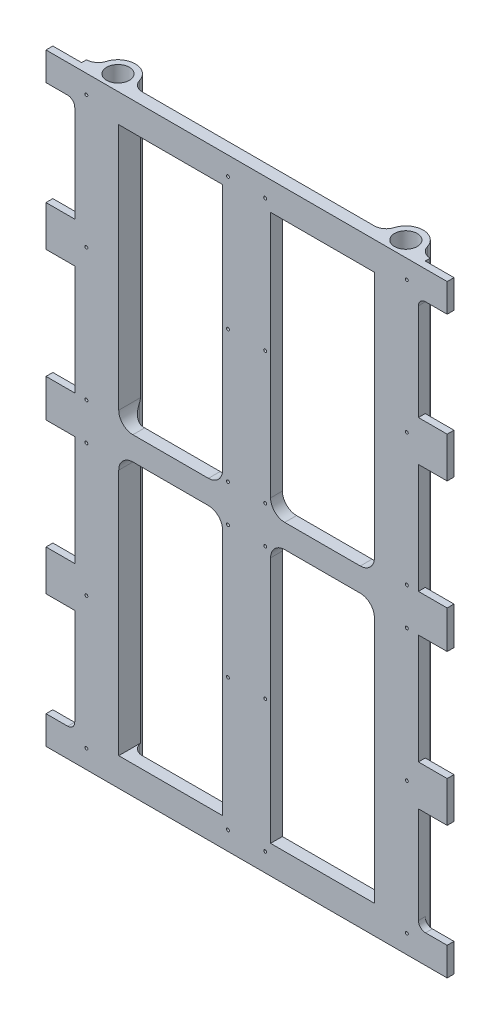
SolidWorks part; units mm, degrees
material "PLA"
ref_plane "Front Plane" through (0, 0, 0) normal (0, 0, 1) x (1, 0, 0)
ref_plane "Top Plane" through (0, 0, 0) normal (0, 1, 0) x (1, 0, 0)
ref_plane "Right Plane" through (0, 0, 0) normal (1, 0, 0) x (0, 0, -1)
other "Center of Mass"
sketch "Sketch1" plane through (0, 0, 0) normal (0, 1, 0) x (1, 0, 0)
  line L19 (85, -5) -> (85, 0)
  line L20 (85, -5) -> (-85, -5)
  line L24 (85, 0) -> (72.8176, 0)
  line L25 (-85, -5) -> (-85, 0)
  line L26 (85, -5) -> (-85, 0) construction
  line L27 (85, 0) -> (-85, -5) construction
  line L28 (0, 0) -> (0, -5) construction
  line L29 (-72.8176, 0) -> (-85, 0)
  line L30 (49.1824, 0) -> (-49.1824, 0)
  circle A29 centre (-61, 1.5) radius 4.825
  arc A30 (-68.1698, 0) -> (-53.8302, 0) centre (-61, 1.5) ccw construction
  arc A31 (-72.8176, 0) -> (-68.0234, 3.5801) centre (-72.8176, 5) ccw
  arc A32 (-53.9766, 3.5801) -> (-49.1824, 0) centre (-49.1824, 5) ccw
  arc A33 (-53.9766, 3.5801) -> (-68.0234, 3.5801) centre (-61, 1.5) ccw
  arc A34 (68.1698, 0) -> (53.8302, 0) centre (61, 1.5) cw construction
  arc A35 (53.9766, 3.5801) -> (68.0234, 3.5801) centre (61, 1.5) cw
  arc A36 (53.9766, 3.5801) -> (49.1824, 0) centre (49.1824, 5) cw
  arc A37 (72.8176, 0) -> (68.0234, 3.5801) centre (72.8176, 5) cw
  circle A38 centre (61, 1.5) radius 4.825
  point P1 (0, -2.5)
  dimension "D3" = 9.65
  dimension "D4" = 6.5
  dimension "D5" = 61
  dimension "D6" = 14.65
  dimension "D1" = 5
  dimension "D2" = 170
extrude "Boss-Extrude1" add sketch "Sketch1" along normal blind 255.6
sketch "Sketch2" plane through (0, 0, 0) normal (0, 0, -1) x (-1, 0, 0)
  line L0 (0, 127.8) -> (-255.8, 127.8) construction
  line L5 (-56.175, 0) -> (-56.175, 550) construction
  line L6 (-54.175, 243.6) -> (-10.175, 243.6)
  line L7 (0, 255.6) -> (-255.8, 255.6) construction
  line L15 (-54.175, 243.6) -> (-54.175, 138.8)
  line L16 (-48.175, 132.8) -> (-16.175, 132.8)
  line L17 (-87.8176, 199.6) -> (-72.8176, 199.6)
  line L18 (-10.175, 243.6) -> (-10.175, 138.8)
  line L31 (-54.175, 243.6) -> (-10.175, 132.8) construction
  line L32 (-54.175, 132.8) -> (-10.175, 243.6) construction
  line L35 (-87.8176, 199.6) -> (-87.8176, 243.6)
  line L36 (-87.8176, 243.6) -> (-75.8176, 243.6)
  line L37 (-72.8176, 199.6) -> (-72.8176, 240.6)
  line L38 (-87.8176, 199.6) -> (-72.8176, 243.6) construction
  line L39 (-87.8176, 243.6) -> (-72.8176, 199.6) construction
  line L41 (-54.175, 122.8) -> (-10.175, 12) construction
  line L42 (-54.175, 12) -> (-10.175, 122.8) construction
  line L46 (-10.175, 12) -> (-10.175, 116.8)
  line L48 (-48.175, 122.8) -> (-16.175, 122.8)
  line L49 (-54.175, 12) -> (-54.175, 116.8)
  line L50 (-54.175, 12) -> (-10.175, 12)
  line L51 (0, 255.6) -> (0, 127.8) construction
  line L52 (54.175, 12) -> (10.175, 122.8) construction
  line L53 (54.175, 122.8) -> (10.175, 12) construction
  line L58 (54.175, 132.8) -> (10.175, 243.6) construction
  line L59 (54.175, 243.6) -> (10.175, 132.8) construction
  line L60 (54.175, 12) -> (10.175, 12)
  line L61 (54.175, 12) -> (54.175, 116.8)
  line L62 (48.175, 122.8) -> (16.175, 122.8)
  line L64 (10.175, 12) -> (10.175, 116.8)
  line L71 (10.175, 243.6) -> (10.175, 138.8)
  line L73 (48.175, 132.8) -> (16.175, 132.8)
  line L74 (54.175, 243.6) -> (54.175, 138.8)
  line L75 (54.175, 243.6) -> (10.175, 243.6)
  line L90 (-72.8176, 135.8) -> (-87.8176, 135.8)
  line L91 (-72.8176, 135.8) -> (-72.8176, 182.4)
  line L92 (-72.8176, 182.4) -> (-87.8176, 182.4)
  line L93 (-87.8176, 135.8) -> (-87.8176, 182.4)
  line L94 (-72.8176, 255.6) -> (-72.8176, 0) construction
  line L95 (-81.8, 205.6) -> (-74.8, 205.6) construction
  line L96 (-74.8, 176.4) -> (-81.8, 176.4) construction
  line L97 (-87.8176, 12) -> (-72.8176, 56) construction
  line L98 (-87.8176, 56) -> (-72.8176, 12) construction
  line L99 (-87.8176, 119.8) -> (-87.8176, 73.2)
  line L100 (-72.8176, 73.2) -> (-87.8176, 73.2)
  line L101 (-72.8176, 119.8) -> (-72.8176, 73.2)
  line L102 (-72.8176, 119.8) -> (-87.8176, 119.8)
  line L103 (-72.8176, 56) -> (-72.8176, 15)
  line L104 (-87.8176, 12) -> (-75.8176, 12)
  line L105 (-87.8176, 56) -> (-87.8176, 12)
  line L106 (-87.8176, 56) -> (-72.8176, 56)
  line L107 (0, 0) -> (0, 127.8) construction
  line L108 (87.8176, 56) -> (72.8176, 12) construction
  line L109 (87.8176, 12) -> (72.8176, 56) construction
  line L110 (87.8176, 243.6) -> (72.8176, 199.6) construction
  line L111 (87.8176, 199.6) -> (72.8176, 243.6) construction
  line L112 (87.8176, 56) -> (72.8176, 56)
  line L113 (87.8176, 56) -> (87.8176, 12)
  line L114 (87.8176, 12) -> (75.8176, 12)
  line L115 (72.8176, 56) -> (72.8176, 15)
  line L116 (72.8176, 119.8) -> (87.8176, 119.8)
  line L117 (72.8176, 119.8) -> (72.8176, 73.2)
  line L118 (72.8176, 73.2) -> (87.8176, 73.2)
  line L119 (87.8176, 119.8) -> (87.8176, 73.2)
  line L120 (87.8176, 135.8) -> (87.8176, 182.4)
  line L121 (72.8176, 182.4) -> (87.8176, 182.4)
  line L122 (72.8176, 135.8) -> (72.8176, 182.4)
  line L123 (72.8176, 135.8) -> (87.8176, 135.8)
  line L124 (72.8176, 199.6) -> (72.8176, 240.6)
  line L125 (87.8176, 243.6) -> (75.8176, 243.6)
  line L126 (87.8176, 199.6) -> (87.8176, 243.6)
  line L127 (87.8176, 199.6) -> (72.8176, 199.6)
  arc A0 (-10.175, 138.8) -> (-16.175, 132.8) centre (-16.175, 138.8) cw
  arc A1 (-54.175, 138.8) -> (-48.175, 132.8) centre (-48.175, 138.8) ccw
  arc A3 (-72.8176, 240.6) -> (-75.8176, 243.6) centre (-75.8176, 240.6) ccw
  arc A6 (-54.175, 116.8) -> (-48.175, 122.8) centre (-48.175, 116.8) cw
  arc A7 (-10.175, 116.8) -> (-16.175, 122.8) centre (-16.175, 116.8) ccw
  arc A8 (10.175, 116.8) -> (16.175, 122.8) centre (16.175, 116.8) cw
  arc A9 (54.175, 116.8) -> (48.175, 122.8) centre (48.175, 116.8) ccw
  arc A14 (54.175, 138.8) -> (48.175, 132.8) centre (48.175, 138.8) cw
  arc A15 (10.175, 138.8) -> (16.175, 132.8) centre (16.175, 138.8) ccw
  arc A18 (-72.8176, 15) -> (-75.8176, 12) centre (-75.8176, 15) cw
  arc A19 (72.8176, 15) -> (75.8176, 12) centre (75.8176, 15) ccw
  arc A20 (72.8176, 240.6) -> (75.8176, 243.6) centre (75.8176, 240.6) cw
  point P0 (-32.175, 188.2)
  point P11 (-80.3176, 221.6)
  point P45 (-32.175, 67.4)
  point P63 (-80.3176, 34)
  point P94 (32.175, 67.4)
  point P97 (32.175, 188.2)
  point P106 (80.3176, 34)
  point P107 (80.3176, 221.6)
  dimension "D8" = 6
  dimension "D9" = 6
  dimension "D1" = 44
  dimension "D2" = 2
  dimension "D3" = 12
  dimension "D4" = 5
  dimension "D5" = 8
  dimension "D6" = 15
  dimension "D7" = 6
extrude "Cut-Extrude2" cut sketch "Sketch2" against normal through all and the other way through all
sketch "Sketch3" plane through (0, 0, 5) normal (0, 0, -1) x (-1, 0, 0)
  line L0 (0, 0) -> (0, 255.6) construction
  line L1 (-49.1824, 0) -> (49.1824, 0) construction
  line L5 (0, 255.6) -> (255.8, 255.6) construction
  line L6 (0, 127.8) -> (-255.8, 127.8) construction
  point P0 (-67.9, 7.9)
  point P1 (-7.9, 7.9)
  point P3 (-7.9, 63.9)
  point P5 (-67.9, 63.9)
  point P7 (-67.9, 119.9)
  point P9 (-7.9, 119.9)
  point P23 (7.9, 119.9)
  point P24 (67.9, 119.9)
  point P25 (67.9, 63.9)
  point P26 (7.9, 63.9)
  point P27 (7.9, 7.9)
  point P28 (67.9, 7.9)
  point P31 (67.9, 503.3)
  point P32 (7.9, 503.3)
  point P33 (7.9, 447.3)
  point P34 (67.9, 447.3)
  point P35 (67.9, 391.3)
  point P36 (7.9, 391.3)
  point P37 (-7.9, 391.3)
  point P38 (-67.9, 391.3)
  point P39 (-67.9, 447.3)
  point P40 (-7.9, 447.3)
  point P41 (-7.9, 503.3)
  point P42 (-67.9, 503.3)
  point P46 (67.9, 247.7)
  point P47 (7.9, 247.7)
  point P48 (7.9, 191.7)
  point P49 (67.9, 191.7)
  point P50 (67.9, 135.7)
  point P51 (7.9, 135.7)
  point P52 (-7.9, 135.7)
  point P53 (-67.9, 135.7)
  point P54 (-67.9, 191.7)
  point P55 (-7.9, 191.7)
  point P56 (-7.9, 247.7)
  point P57 (-67.9, 247.7)
hole_wizard "Ø1.25 (1.25) Diameter Hole1" positions "Sketch3" profile "Sketch4" hole size "Ø1.25" standard "ANSI Metric" end condition through all
sketch "Sketch4" plane through (67.9, 7.9, 5) normal (1, 0, 0) x (0, -1, 0)
  line L0 (0, 0) -> (0, 13.825)
  line L1 (0, 13.825) -> (0.625, 13.825)
  line L2 (0.625, 13.825) -> (0.625, 0)
  line L5 (0.625, 0) -> (0, 0)
  line L11 (0, -6.35) -> (0, 107.95) construction
  dimension "Thru Hole Dia." = 1.25
  dimension "Thru Hole Depth" = 13.825
sketch "Sketch5" plane through (0, 0, 0) normal (0, 0, -1) x (-1, 0, 0)
  line L0 (-255.8, 0) -> (-72.8176, 0) construction
  line L1 (-72.8176, 255.6) -> (-88.658, 255.6)
  line L2 (0, 255.6) -> (0, 127.8) construction
  line L3 (0, 127.8) -> (-255.8, 127.8) construction
  line L4 (-72.8176, 255.6) -> (-72.8176, 0)
  line L5 (-72.8176, 0) -> (-88.658, 0)
  line L6 (-88.658, 255.6) -> (-88.658, 0)
  line L7 (88.658, 255.6) -> (88.658, 0)
  line L8 (72.8176, 0) -> (88.658, 0)
  line L9 (72.8176, 255.6) -> (72.8176, 0)
  line L10 (72.8176, 255.6) -> (88.658, 255.6)
  circle A24 centre (-67.9, 247.7) radius 1.5
  circle A25 centre (-7.9, 247.7) radius 1.5
  circle A26 centre (-67.9, 191.7) radius 1.5
  circle A27 centre (-67.9, 135.7) radius 1.5
  circle A28 centre (-7.9, 135.7) radius 1.5
  circle A29 centre (-7.9, 191.7) radius 1.5
  circle A48 centre (7.9, 191.7) radius 1.5
  circle A49 centre (7.9, 135.7) radius 1.5
  circle A50 centre (67.9, 135.7) radius 1.5
  circle A51 centre (67.9, 191.7) radius 1.5
  circle A52 centre (7.9, 247.7) radius 1.5
  circle A53 centre (67.9, 247.7) radius 1.5
  circle A54 centre (67.9, 7.9) radius 1.5
  circle A55 centre (7.9, 7.9) radius 1.5
  circle A56 centre (67.9, 63.9) radius 1.5
  circle A57 centre (67.9, 119.9) radius 1.5
  circle A58 centre (7.9, 119.9) radius 1.5
  circle A59 centre (7.9, 63.9) radius 1.5
  circle A60 centre (-7.9, 63.9) radius 1.5
  circle A61 centre (-7.9, 119.9) radius 1.5
  circle A62 centre (-67.9, 119.9) radius 1.5
  circle A63 centre (-67.9, 63.9) radius 1.5
  circle A64 centre (-7.9, 7.9) radius 1.5
  circle A65 centre (-67.9, 7.9) radius 1.5
  dimension "D1" = 3
extrude "Cut-Extrude3" cut sketch "Sketch5" along normal through all
sketch "Sketch6" plane through (0, 0, 0) normal (0, 0, -1) x (-1, 0, 0)
  line L0 (255.8, 255.6) -> (72.8176, 255.6) construction
  line L1 (72.8176, 0) -> (88.6, 0)
  line L2 (72.8176, 0) -> (72.8176, 255.6)
  line L3 (72.8176, 255.6) -> (88.6, 255.6)
  line L4 (88.6, 0) -> (88.6, 255.6)
  line L5 (0, 0) -> (0, 127.8) construction
  line L6 (-88.6, 0) -> (-88.6, 255.6)
  line L7 (-72.8176, 255.6) -> (-88.6, 255.6)
  line L8 (-72.8176, 0) -> (-72.8176, 255.6)
  line L9 (-72.8176, 0) -> (-88.6, 0)
extrude "Cut-Extrude4" cut sketch "Sketch6" against normal blind 2.1
equation "\"rod_d\"= 9.65"
equation "\"big_bearing_id\"= 140mm"
equation "\"rod_offset_c2c\"= \"big_bearing_id\" / 2 - \"rod_d\" / 2 - 1.5"
